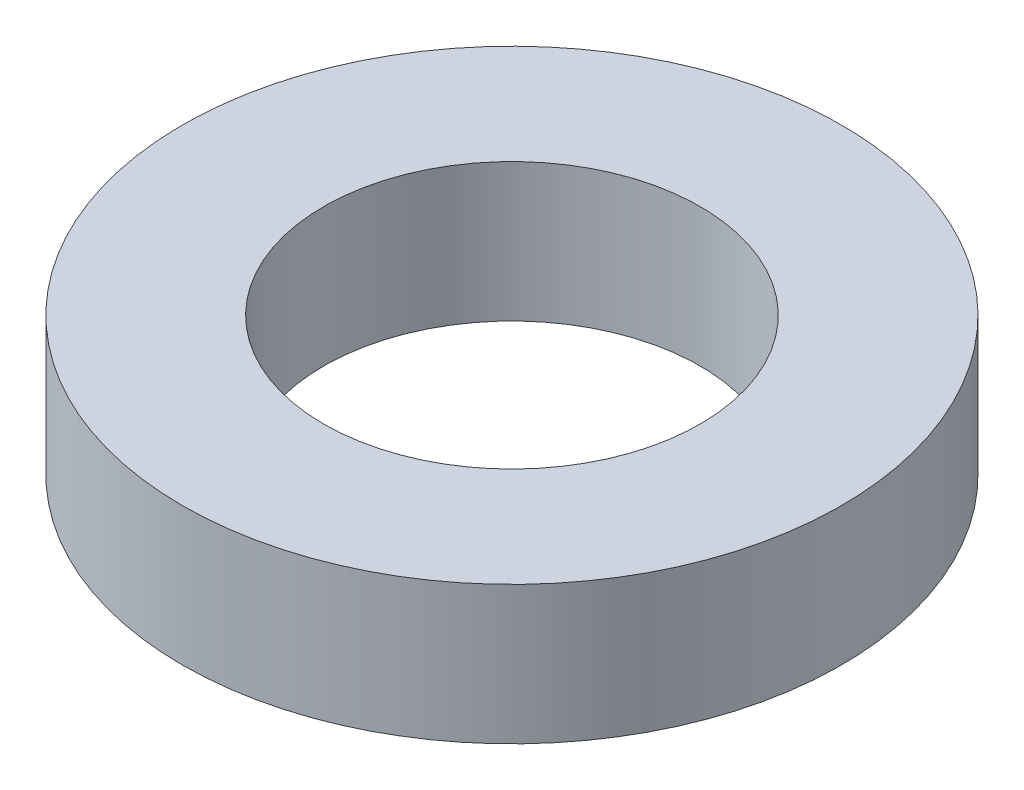
SolidWorks part; units mm, degrees
ref_plane "Front Plane" through (0, 0, 0) normal (0, 0, 1) x (1, 0, 0)
ref_plane "Top Plane" through (0, 0, 0) normal (0, 1, 0) x (1, 0, 0)
ref_plane "Right Plane" through (0, 0, 0) normal (1, 0, 0) x (0, 0, -1)
sketch "Sketch1" plane through (0, 0, 0) normal (0, 1, 0) x (1, 0, 0)
  circle A0 centre (0, 0) radius 52.5
  dimension "FLANGE_OD" = 105
extrude "Boss-Extrude1" add sketch "Sketch1" along normal blind 22
sketch "Sketch2" plane through (0, 0, 0) normal (0, 1, 0) x (1, 0, 0)
  circle A0 centre (0, 0) radius 30
  dimension "BORE_D" = 60
extrude "Cut-Extrude1" cut sketch "Sketch2" along normal through all
sketch "Sketch3" plane through (0, 22, 0) normal (0, 1, 0) x (1, 0, 0)
  circle A0 centre (0, 0) radius 23.1448 construction
  circle A1 centre (-23.1448, 0) radius 1.6974
  dimension "BOLT_D" = 3.3947
  dimension "BOLT_PCD" = 46.2895
extrude "Cut-Extrude2" cut sketch "Sketch3" against normal blind 20.8111 rebuild error yes
pattern_circular "CirPattern1" count 8 over 360 rebuild error yes
